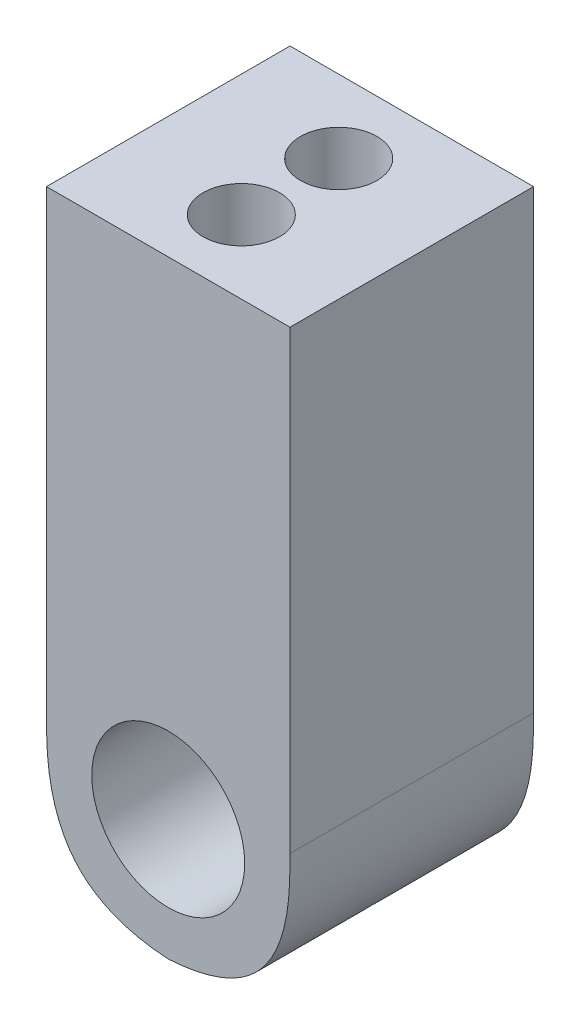
SolidWorks part; units mm, degrees
ref_plane "Front Plane" through (0, 0, 0) normal (0, 0, 1) x (1, 0, 0)
ref_plane "Top Plane" through (0, 0, 0) normal (0, 1, 0) x (1, 0, 0)
ref_plane "Right Plane" through (0, 0, 0) normal (1, 0, 0) x (0, 0, -1)
sketch "Sketch1" plane through (0, 0, 0) normal (0, 0, 1) x (1, 0, 0)
  line L1 (-6.35, 6.35) -> (6.35, 6.35)
  line L2 (-6.35, 6.35) -> (-6.35, -6.35)
  line L3 (-6.35, -6.35) -> (6.35, -6.35)
  line L4 (6.35, 6.35) -> (6.35, -6.35)
  line L5 (-6.35, 6.35) -> (6.35, -6.35) construction
  line L6 (-6.35, -6.35) -> (6.35, 6.35) construction
  line L7 (-6.35, 6.35) -> (6.35, 6.35)
  line L8 (-6.35, 6.35) -> (-6.35, 25.4)
  line L9 (-6.35, 25.4) -> (6.35, 25.4)
  line L10 (6.35, 6.35) -> (6.35, 25.4)
  circle A0 centre (0, 0) radius 3.9878
  point P0 (0, 0)
  dimension "D2" = 7.9756
  dimension "D1" = 12.7
  dimension "D3" = 19.05
  dimension "D4" = 12.7
extrude "Boss-Extrude1" add sketch "Sketch1" against normal blind 12.7 contours L1 L10 L9 L8 | L4 L1 L2 L3 A0 | A0 region at (0, 15.875, 0) region at (0, 6.1704, 0) region at (0, 0, 0)
fillet "Fillet1" radius 7.9756 2 edges at (-6.35, -6.35, -6.35) (6.35, -6.35, -6.35) curvature continuous yes
sketch "Sketch3" plane through (0, 25.4, 0) normal (0, 1, 0) x (1, 0, 0)
  line L0 (0, 12.7) -> (0, 0) construction
  line L1 (6.35, 8.89) -> (-6.35, 8.89)
  line L2 (-6.35, 3.81) -> (6.35, 3.81)
  line L4 (-6.35, 0) -> (6.35, 0)
  line L5 (6.35, 0) -> (6.35, 12.7)
  line L6 (6.35, 12.7) -> (-6.35, 12.7)
  line L7 (-6.35, 12.7) -> (-6.35, 0)
  line L8 (-6.35, 0) -> (6.35, 0)
  line L9 (6.35, 0) -> (6.35, 12.7)
  line L10 (6.35, 12.7) -> (-6.35, 12.7)
  line L11 (-6.35, 12.7) -> (-6.35, 0)
  circle A0 centre (0, 8.89) radius 1.9939
  circle A1 centre (0, 3.81) radius 1.9939
  dimension "D3" = 3.9878
  dimension "D4" = 3.9878
  dimension "D2" = 3.81
  dimension "D1" = 0
extrude "Cut-Extrude2" cut sketch "Sketch3" against normal blind 6.35 contours L1 L0 A0 | A0 L0 L1 | L0 A0 L1 | L0 L1 A0 | A1 L0 L2 | L2 L0 A1 | L0 L2 A1 | L0 A1 L2 region at (0.8462, 25.4, -9.7362) region at (-0.8462, 25.4, -9.7362) region at (0.8462, 25.4, -8.0438) region at (-0.8462, 25.4, -8.0438) region at (0.8462, 25.4, -4.6562) region at (-0.8462, 25.4, -4.6562) region at (0.8462, 25.4, -2.9638) region at (-0.8462, 25.4, -2.9638)
extrude "Cut-Extrude3" cut sketch "Sketch1<3>" against normal blind 6.35 contours A0
sketch "Sketch1<3>" plane through (0, 0, 0) normal (0, 0, 1) x (1, 0, 0) same geometry as "Sketch1"
